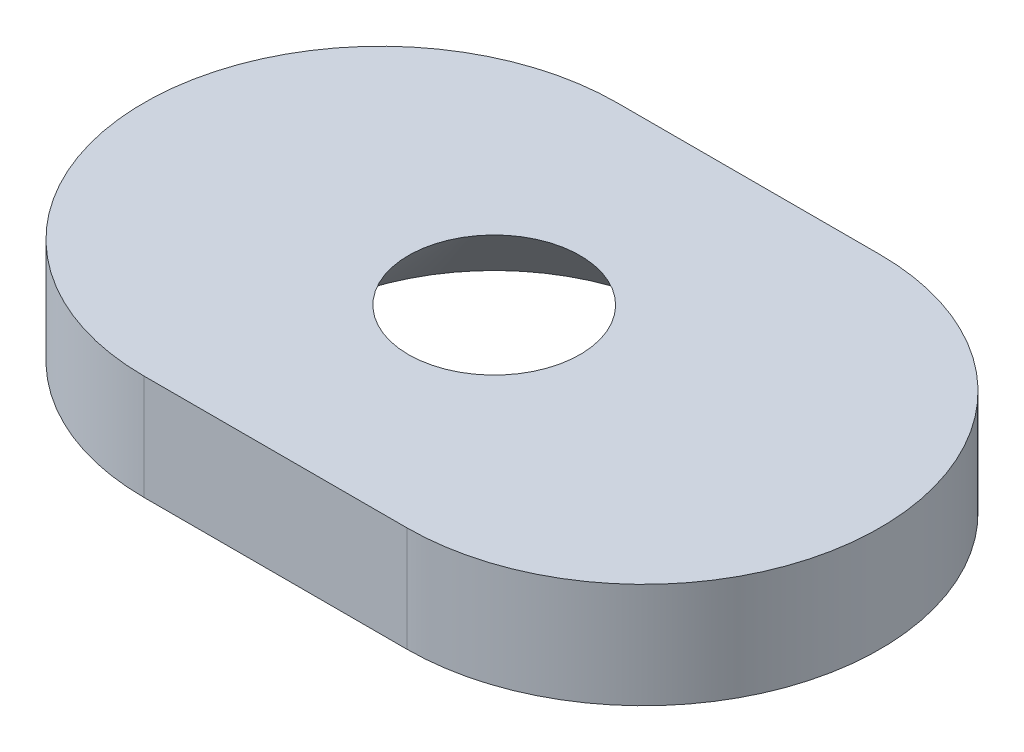
SolidWorks part; units mm, degrees
ref_plane "Plano frontal" through (0, 0, 0) normal (0, 0, 1) x (1, 0, 0)
ref_plane "Plano superior" through (0, 0, 0) normal (0, 1, 0) x (1, 0, 0)
ref_plane "Plano direito" through (0, 0, 0) normal (1, 0, 0) x (0, 0, -1)
sketch "Esboço2" plane through (0, 0, 0) normal (0, 1, 0) x (1, 0, 0)
  line L0 (-4.3243, 0) -> (5.6757, 0) construction
  line L1 (-4.3243, 9) -> (5.6757, 9)
  line L2 (-4.3243, -9) -> (5.6757, -9)
  arc A0 (-4.3243, 9) -> (-4.3243, -9) centre (-4.3243, 0) ccw
  arc A1 (5.6757, -9) -> (5.6757, 9) centre (5.6757, 0) ccw
  point P3 (0.6757, 0)
  dimension "D1" = 10
  dimension "D3" = 18
extrude "Ressalto-extrusão1" add sketch "Esboço2" along normal blind 4
sketch "Esboço3" plane through (0, 0, 0) normal (0, -1, 0) x (-1, 0, 0)
  circle A0 centre (0, 0) radius 3.265
  point P0 (0, 0)
  dimension "D1" = 6.53
extrude "Corte-extrusão1" cut sketch "Esboço3" against normal blind 10
chamfer "Chanfro1" distance 4 1 edges at (0, 0, -3.265)
